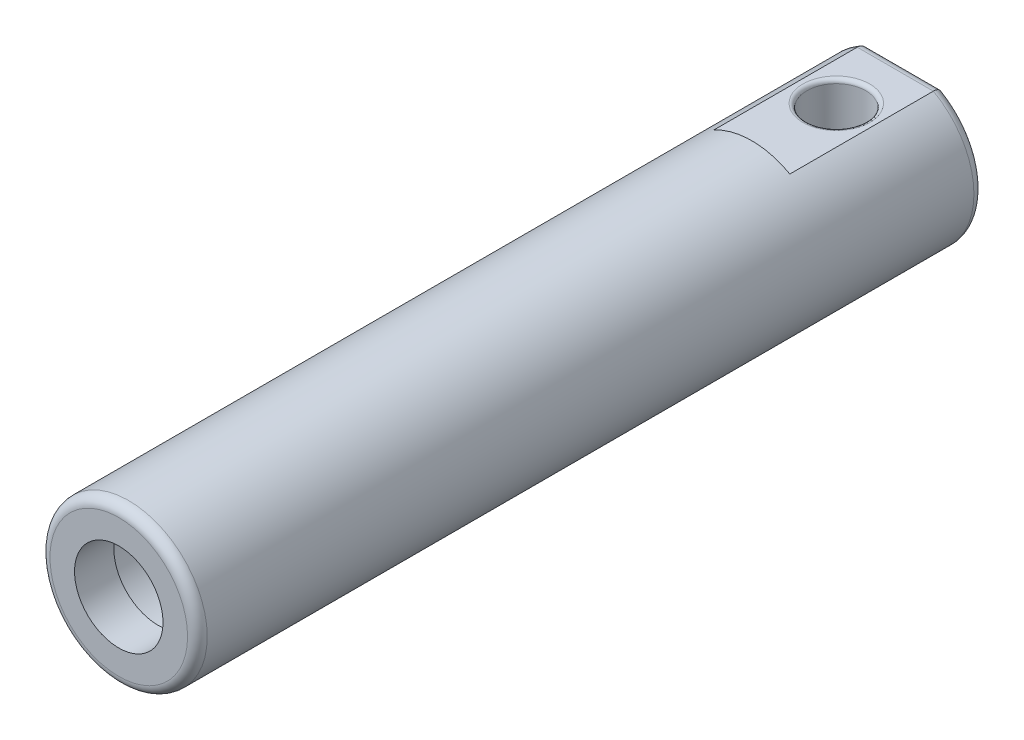
SolidWorks part; units mm, degrees
material "Alloy Steel"
ref_plane "Front" through (0, 0, 0) normal (0, 0, 1) x (1, 0, 0)
ref_plane "Top" through (0, 0, 0) normal (0, 1, 0) x (1, 0, 0)
ref_plane "Right" through (0, 0, 0) normal (1, 0, 0) x (0, 0, -1)
sketch "Sketch2" plane through (0, 0, 0) normal (0, 0, 1) x (1, 0, 0)
  circle A0 centre (0, 0) radius 40
  dimension "D1" = 80
extrude "Boss-Extrude1" add sketch "Sketch2" along normal blind 320
sketch "Sketch3" plane through (0, 0, 0) normal (0, 0, -1) x (-1, 0, 0)
  circle A0 centre (0, 0) radius 30
  dimension "60" = 60
extrude "Cut-Extrude1" cut sketch "Sketch3" against normal blind 300
sketch "Sketch4" plane through (0, 0, 320) normal (0, 0, 1) x (1, 0, 0)
  circle A0 centre (0, 0) radius 22.5
  dimension "D1" = 45
extrude "Cut-Extrude2" cut sketch "Sketch4" against normal up to next
sketch "Sketch5" plane through (0, 0, 0) normal (0, 0, -1) x (-1, 0, 0)
  circle A0 centre (0, 0) radius 40 construction
  circle A1 centre (0, 0) radius 40
extrude "Boss-Extrude2" add sketch "Sketch5" along normal blind 80
ref_plane "Plane1" through (0, 40, 0) normal (0, 1, 0) x (1, 0, 0)
sketch "Sketch6" plane through (0, 40, 0) normal (0, 1, 0) x (1, 0, 0)
  line L1 (20, 80) -> (-20, 80)
  line L2 (20, 80) -> (20, 2)
  line L3 (20, 2) -> (-20, 2)
  line L4 (-20, 80) -> (-20, 2)
  line L5 (20, 80) -> (-20, 2) construction
  line L6 (20, 2) -> (-20, 80) construction
  line L7 (40, 80) -> (-40, 80) construction
  point P0 (0, 41)
  dimension "D1" = 78
  dimension "D2" = 40
extrude "Cut-Extrude3" cut sketch "Sketch6" against normal blind 5
mirror "Mirror1" about plane through (0, 0, 0) normal (0, 1, 0) of "Cut-Extrude3"
sketch "Sketch7" plane through (0, 35, 0) normal (0, 1, 0) x (1, 0, 0)
  line L1 (19.3649, 80) -> (-19.3649, 80) construction
  circle A0 centre (0, 45) radius 15
  point P2 (0, 0)
  point P3 (0, 0)
  point P4 (0, 0)
  point P5 (0, 0)
  dimension "D1" = 30
  dimension "D2" = 35
extrude "Cut-Extrude4" cut sketch "Sketch7" against normal through all
fillet "Fillet2" radius 5 5 edges at (0, -35, -80) (0, 35, -80) (40, 0, -80) (-40, 0, -80) (40, 0, 320)
fillet "Fillet3" radius 2 2 edges at (0, -35, -30) (0, 35, -30)
